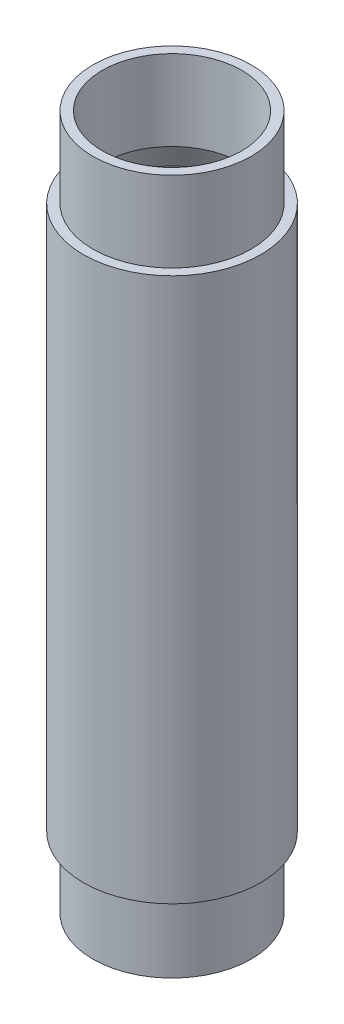
SolidWorks part; units mm, degrees
ref_plane "Front Plane" through (0, 0, 0) normal (0, 0, 1) x (1, 0, 0)
ref_plane "Top Plane" through (0, 0, 0) normal (0, 1, 0) x (1, 0, 0)
ref_plane "Right Plane" through (0, 0, 0) normal (1, 0, 0) x (0, 0, -1)
sketch "Sketch1" plane through (0, 0, 0) normal (0, 1, 0) x (1, 0, 0)
  circle A0 centre (0, 0) radius 33.5
  circle A1 centre (0, 0) radius 37.5
  dimension "D1" = 4
  dimension "D2" = 75
extrude "Boss-Extrude1" add sketch "Sketch1" along normal blind 230
sketch "Sketch2" plane through (0, 0, 0) normal (0, -1, 0) x (1, 0, 0)
  circle A0 centre (0, 0) radius 33.5
  circle A1 centre (0, 0) radius 29.5
  circle A2 centre (0, 0) radius 33.5 construction
  dimension "D1" = 4
extrude "Boss-Extrude2" add sketch "Sketch2" along normal blind 30 and the other way blind 4
extrude "Boss-Extrude3" add sketch "Sketch2<2>" against normal blind 34 from offset 230 offset against normal yes
sketch "Sketch2<2>" plane through (0, 0, 0) normal (0, -1, 0) x (1, 0, 0) same geometry as "Sketch2"
sketch "Sketch3" plane through (0, 0, 0) normal (1, 0, 0) x (0, 0, -1)
  line L0 (-29.5, 230) -> (29.5, 230) construction
  line L1 (-33.5, 220) -> (-29.5, 230)
  line L2 (-29.5, 230) -> (-33.5, 230)
  line L3 (-33.5, 230) -> (-33.5, 220)
  line L6 (0, 147.317) -> (0, -39.51) construction
  line L7 (-29.5, 4) -> (-33.5, 14)
  line L8 (-33.5, 14) -> (-33.5, 4)
  line L9 (-33.5, 4) -> (-29.5, 4)
  line L10 (29.5, 4) -> (-29.5, 4) construction
  dimension "D1" = 33.5
  dimension "D2" = 4
  dimension "D3" = 10
  dimension "D4" = 10
  dimension "D5" = 33.5
  dimension "D6" = 0
  dimension "D7" = 10
revolve "Revolve2" add sketch "Sketch3" angle 360 about L6
